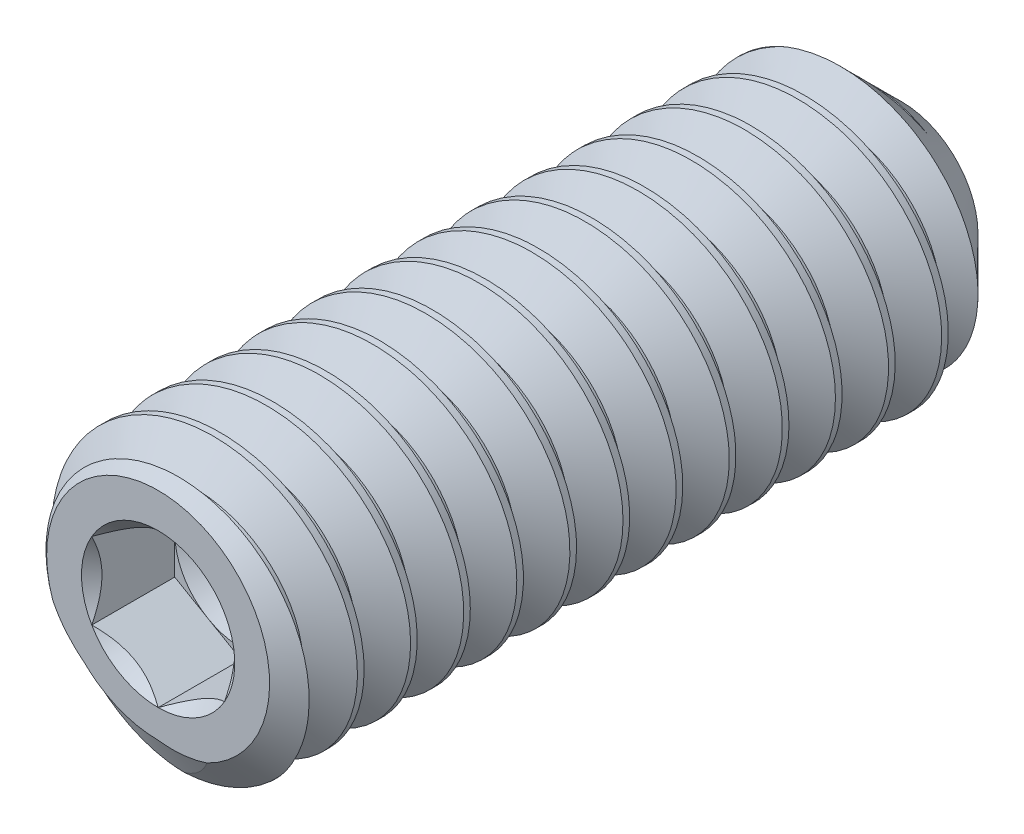
SolidWorks part; units mm, degrees
ref_plane "Front" through (0, 0, 0) normal (0, 0, 1) x (1, 0, 0)
ref_plane "Top" through (0, 0, 0) normal (0, 1, 0) x (1, 0, 0)
ref_plane "Right" through (0, 0, 0) normal (1, 0, 0) x (0, 0, -1)
sketch "Sketch22" plane through (0, 0, 0) normal (1, 0, 0) x (0, 0, -1)
  line L0 (-5.2134, 0) -> (-5.2134, 1.6662)
  line L1 (-5.2134, 1.6662) -> (-4.9217, 2.0828)
  line L2 (-4.9217, 2.0828) -> (4.9576, 2.0828)
  line L3 (4.9576, 2.0828) -> (5.8991, 1.1413)
  line L4 (5.8991, 1.1413) -> (5.2134, 0)
  line L5 (5.2134, 0) -> (-5.2134, 0)
  line L6 (5.2134, 0) -> (5.8991, 0) construction
  line L7 (5.8991, 0) -> (5.8991, 1.1413) construction
  line L8 (5.8991, -1.1413) -> (5.2134, 0) construction
  line L9 (-4.9217, -2.0828) -> (4.9576, -2.0828) construction
  line L10 (5.8991, -2.0828) -> (5.8991, 2.0828) construction
  line L11 (5.8991, 2.0828) -> (5.1054, 2.0828) construction
  point P11 (3.9148, -2.0828)
  point P15 (5.8991, 0)
  dimension "D3" = 35
  dimension "D5" = 118
  dimension "D6" = 45
  dimension "D7" = 3.3325
  dimension "D1" = 1.9844
revolve "Revolve1" add sketch "Sketch22" angle 360 about L6
ref_plane "Plane1" through (0, 0, -5.8991) normal (0, 0, 1) x (1, 0, 0)
sketch "Sketch27" plane through (0, 0, -5.8991) normal (0, 0, 1) x (1, 0, 0)
  circle A0 centre (0, 0) radius 2.0828 construction
  circle A1 centre (0, 0) radius 2.0828
sketch "Sketch23" plane through (0, 0, 5.2134) normal (0, 0, 1) x (1, 0, 0)
  line L1 (0, 1.1457) -> (-0.9922, 0.5728)
  line L2 (-0.9922, 0.5728) -> (-0.9922, -0.5728)
  line L3 (-0.9922, -0.5728) -> (0, -1.1457)
  line L4 (0, -1.1457) -> (0.9922, -0.5728)
  line L5 (0.9922, -0.5728) -> (0.9922, 0.5728)
  line L6 (0.9922, 0.5728) -> (0, 1.1457)
  circle A0 centre (0, 0) radius 0.9922 construction
extrude "Cut-Extrude10" cut sketch "Sketch23" against normal blind 1.2402
sketch "Sketch24" plane through (0, 0, 5.2134) normal (0, 0, 1) x (1, 0, 0)
  circle A0 centre (0, 0) radius 1.1457
extrude "Cut-Extrude11" cut sketch "Sketch24" against normal through all draft 45
sketch "Sketch26" plane through (0, 0, 3.9731) normal (0, 0, 1) x (1, 0, 0)
  circle A0 centre (0, 0) radius 0.9922 construction
  circle A1 centre (0, 0) radius 0.9922
extrude "Cut-Extrude12" cut sketch "Sketch26" against normal through all draft 60
sketch "Sketch31" plane through (0, 0, 0) normal (1, 0, 0) x (0, 0, -1)
  line L2 (5.2134, 0) -> (5.8991, -1.1413)
  line L3 (5.8991, 1.1413) -> (5.2134, 0)
ref_axis "Center Axis1" through (0, 0, -42.9554) along (0, 0, 1)
ref_plane "Contact Plane1" through (0, 0, -5.8991) normal (0, 0, 1) x (1, 0, 0)
ref_plane "Contact Plane2" through (0, 0, 5.2134) normal (0, 0, 1) x (1, 0, 0)
curve "Helix/Spiral1" pitch 0.7937 height 11.9062 radius 2.0828 centre (0, 0, -5.8991) axis (0, 0, 1) start towards (0, 1, 0)
sketch "Sketch32" plane through (0, 0, 0) normal (1, 0, 0) x (0, 0, -1)
  line L0 (5.8495, 2.1687) -> (6.6433, 2.1687) construction
  line L1 (6.6433, 2.1687) -> (6.2464, 1.4813) construction
  line L2 (6.2464, 1.4813) -> (5.8495, 2.1687) construction
  line L3 (5.8991, 2.0828) -> (5.1054, 2.0828) construction
  line L4 (6.2464, 1.4813) -> (6.2464, 1.5672) construction
  line L5 (6.2464, 2.1687) -> (6.2464, 2.0828) construction
  line L6 (6.1968, 1.5672) -> (6.296, 1.5672)
  line L7 (5.8991, 2.0828) -> (6.5937, 2.0828) construction
  line L8 (5.8743, 2.1258) -> (6.6185, 2.1258)
  line L9 (5.8743, 2.1258) -> (6.1968, 1.5672)
  line L10 (6.296, 1.5672) -> (6.6185, 2.1258)
  point P11 (6.2464, 1.5672)
  point P13 (6.2464, 2.0828)
  point P17 (6.2464, 2.1258)
  dimension "D1" = 0.0992
sweep "Cut-Sweep1" cut profiles "Sketch32" path "Helix/Spiral1"
equation "\"D7@Sketch22\"=\"Dia@Sketch22\"*.8"
equation "\"D3@Helix/Spiral1\"=\"Length@Sketch22\" + \"Pitch@Sketch22\"l1\""
equation "\"hex Depth@Cut-Extrude10\" = \"Hex@Sketch23\" * .625"
equation "\"D1@Sketch22\"=\"Pitch@Sketch22\"*2.5"
equation "\"D4@Helix/Spiral1\"=\"Pitch@Sketch22\""
equation "\"D1@Sketch32\"=\"Pitch@Sketch22\"*.125"
